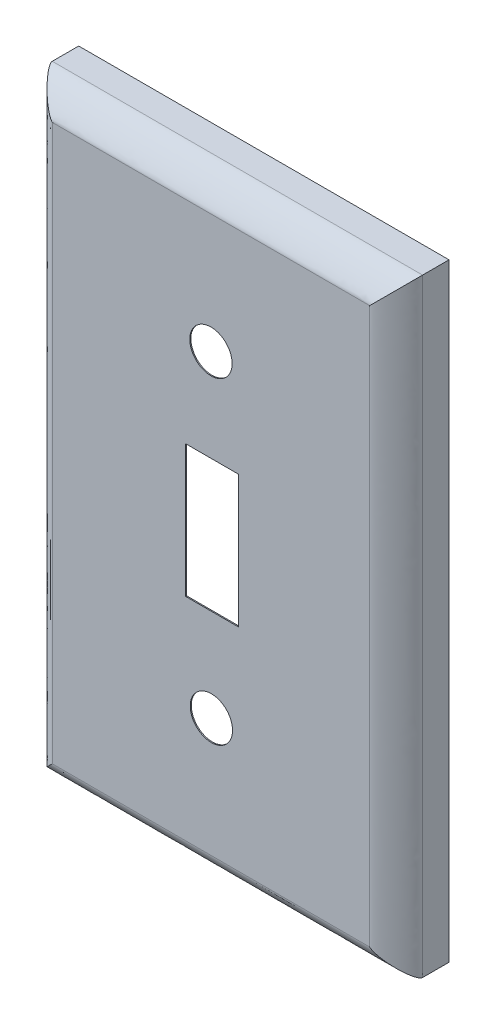
SolidWorks part; units mm, degrees
ref_plane "Front Plane" through (0, 0, 0) normal (0, 0, 1) x (1, 0, 0)
ref_plane "Top Plane" through (0, 0, 0) normal (0, 1, 0) x (1, 0, 0)
ref_plane "Right Plane" through (0, 0, 0) normal (1, 0, 0) x (0, 0, -1)
sketch "Sketch1" plane through (0, 0, 0) normal (0, 0, 1) x (1, 0, 0)
  line L1 (-35.0785, 41.2435) -> (34.9215, 41.2435)
  line L2 (-35.0785, 41.2435) -> (-35.0785, -73.7565)
  line L3 (-35.0785, -73.7565) -> (34.9215, -73.7565)
  line L4 (34.9215, 41.2435) -> (34.9215, -73.7565)
  dimension "D1" = 115
  dimension "D2" = 70
extrude "Boss-Extrude1" add sketch "Sketch1" along normal blind 10
fillet "Fillet3" radius 5 4 edges at (-0.0785, -73.7565, 10) (34.9215, -16.2565, 10) (-0.0785, 41.2435, 10) (-35.0785, -16.2565, 10) conic rho 0.2
shell "Shell1" thickness 0.2 removed face at (-0.0785, -16.2565, 0)
sketch "Sketch2" plane through (0, 0, 10) normal (0, 0, 1) x (1, 0, 0)
  line L0 (34.9215, -73.7565) -> (-35.0785, -73.7565) construction
  line L1 (-4.8785, -3.7565) -> (5.1215, -3.7565)
  line L2 (-4.8785, -3.7565) -> (-4.8785, -28.7565)
  line L3 (-4.8785, -28.7565) -> (5.1215, -28.7565)
  line L4 (5.1215, -3.7565) -> (5.1215, -28.7565)
  line L5 (-34.8785, -73.5565) -> (-34.8785, 41.0435) construction
  dimension "D1" = 25
  dimension "D2" = 45
  dimension "D3" = 10
  dimension "D4" = 30
extrude "Cut-Extrude1" cut sketch "Sketch2" against normal through all
sketch "Sketch3" plane through (0, 0, 10) normal (0, 0, 1) x (1, 0, 0)
  line L0 (34.9215, -73.7565) -> (-35.0785, -73.7565) construction
  line L2 (-35.0785, -73.7565) -> (-35.0785, 41.2435) construction
  circle A0 centre (-0.0785, 13.7435) radius 4
  circle A1 centre (0, -46.2565) radius 4
  dimension "D1" = 8
  dimension "D2" = 8
  dimension "D3" = 27.5
  dimension "D4" = 60
  dimension "D5" = 35
extrude "Cut-Extrude2" cut sketch "Sketch3" against normal through all
